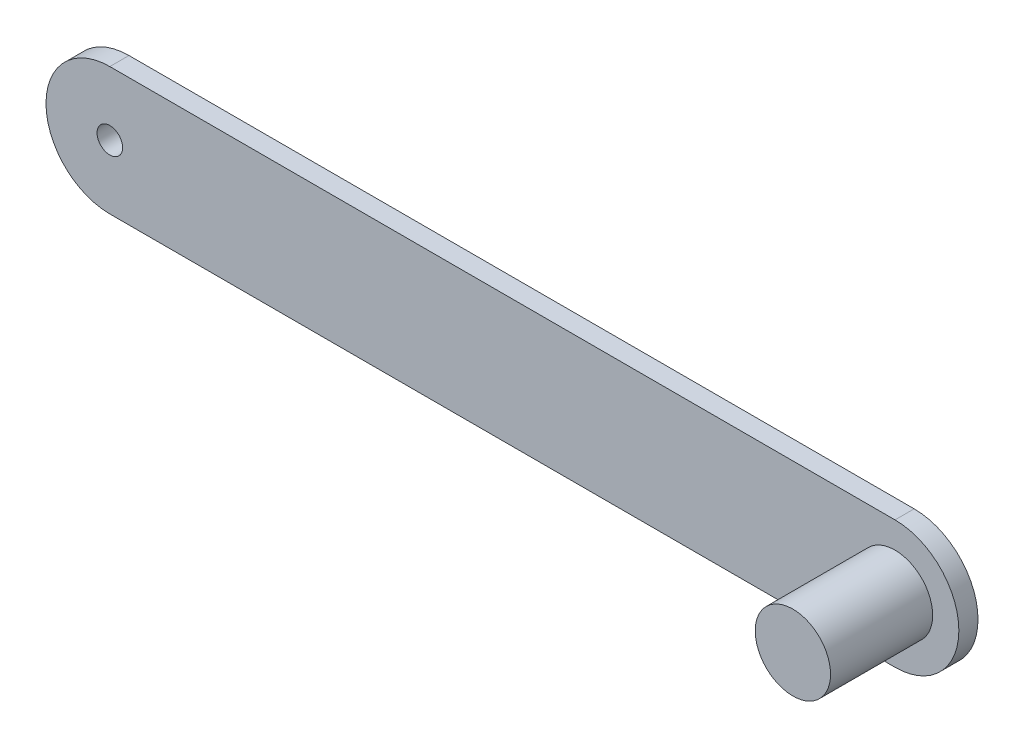
SolidWorks part; units mm, degrees
ref_plane "Front Plane" through (0, 0, 0) normal (0, 0, 1) x (1, 0, 0)
ref_plane "Top Plane" through (0, 0, 0) normal (0, 1, 0) x (1, 0, 0)
ref_plane "Right Plane" through (0, 0, 0) normal (1, 0, 0) x (0, 0, -1)
sketch "Sketch1" plane through (0, 0, 0) normal (0, 0, 1) x (1, 0, 0)
  line L0 (0, 5) -> (61.5, 5)
  line L6 (0, -5) -> (61.5, -5)
  arc A2 (0, 5) -> (0, -5) centre (0, 0) ccw
  arc A3 (61.5, -5) -> (61.5, 5) centre (61.5, 0) ccw
  dimension "D1" = 10
  dimension "D2" = 61.5
extrude "Boss-Extrude4" add sketch "Sketch1" along normal blind 1.5
sketch "Sketch4" plane through (0, 0, 1.5) normal (0, 0, 1) x (1, 0, 0)
  circle A0 centre (0, 0) radius 1
  dimension "D1" = 2
extrude "Cut-Extrude1" cut sketch "Sketch4" against normal through all
sketch "Sketch5" plane through (0, 0, 1.5) normal (0, 0, 1) x (1, 0, 0)
  circle A0 centre (61.5, 0) radius 2.95
  arc A3 (61.5, -5) -> (61.5, 5) centre (61.5, 0) ccw construction
  point P2 (0, 0)
  dimension "D1" = 5.9
extrude "Boss-Extrude5" add sketch "Sketch5" along normal blind 8
